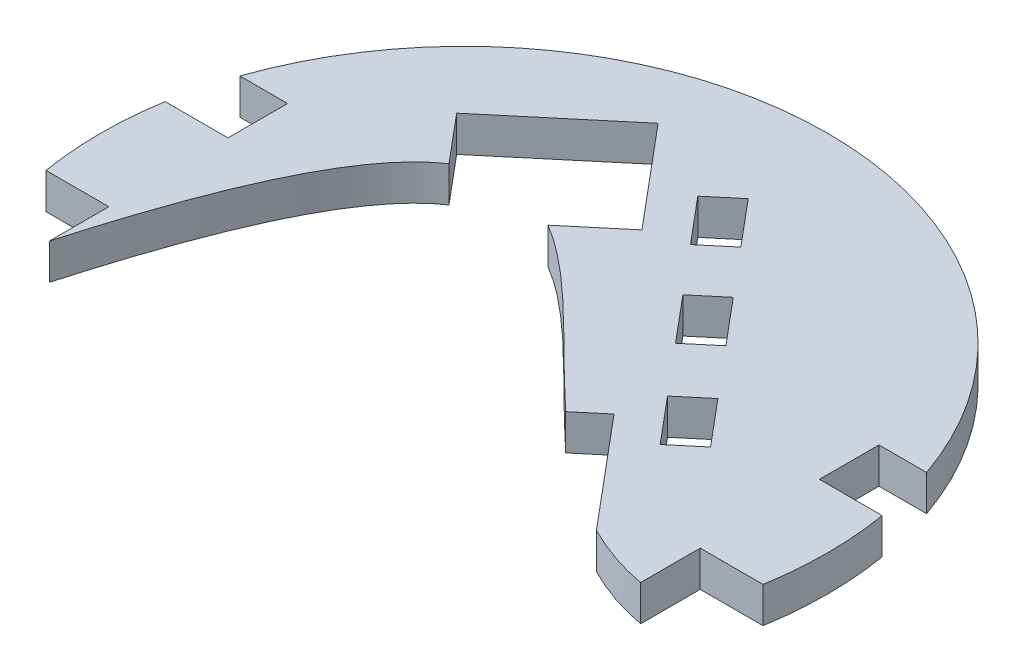
SolidWorks part; units mm, degrees
ref_plane "Alzado" through (0, 0, 0) normal (0, 0, 1) x (1, 0, 0)
ref_plane "Planta" through (0, 0, 0) normal (0, 1, 0) x (1, 0, 0)
ref_plane "Vista lateral" through (0, 0, 0) normal (1, 0, 0) x (0, 0, -1)
sketch "Croquis1" plane through (0, 0, 0) normal (0, 1, 0) x (1, 0, 0)
  circle A0 centre (0, 0) radius 30.5
extrude "Saliente-Extruir1" add sketch "Croquis1" along normal blind 3
sketch "Croquis2" plane through (0, 3, 0) normal (0, 1, 0) x (1, 0, 0)
  circle A0 centre (0, 0) radius 2
extrude "Cortar-Extruir1" cut sketch "Croquis2" against normal blind 4
sketch "Croquis5" plane through (0, 3, 0) normal (0, 1, 0) x (1, 0, 0)
  line L0 (0, 0) -> (0, 10)
  line L1 (28.8141, -5) -> (30.0874, -5)
  line L2 (28.8141, 5) -> (30.0874, 5)
  line L3 (-24.8141, 10) -> (-28.8141, 10)
  line L4 (24.8141, -5) -> (24.8141, -10)
  line L5 (-24.8141, -10) -> (-28.8141, -10)
  line L6 (24.8141, -5) -> (28.8141, -5)
  line L7 (24.8141, 5) -> (24.8141, 10)
  line L8 (-24.8141, 5) -> (-28.8141, 5)
  line L9 (-24.8141, 5) -> (-24.8141, 10)
  line L10 (-24.8141, -5) -> (-28.8141, -5)
  line L11 (-24.8141, -5) -> (-24.8141, -10)
  line L12 (24.8141, 5) -> (28.8141, 5)
  line L13 (24.8141, -10) -> (28.8141, -10)
  line L14 (24.8141, 10) -> (28.8141, 10)
  line L15 (-28.8141, 5) -> (-30.0874, 5)
  line L16 (-28.8141, -5) -> (-30.0874, -5)
  circle A1 centre (0, 0) radius 30.5 construction
  arc A2 (-28.8141, 10) -> (-30.0874, 5) centre (0, 0) ccw
  arc A3 (28.8141, 10) -> (28.8141, -10) centre (0, 0) cw
  arc A4 (-30.0874, -5) -> (-28.8141, -10) centre (0, 0) ccw
  arc A5 (30.0874, -5) -> (28.8141, -10) centre (0, 0) cw
  arc A6 (28.8141, 10) -> (30.0874, 5) centre (0, 0) cw
  circle M2 centre (0, 0) radius 30.5
extrude "Cortar-Extruir3" cut sketch "Croquis5" against normal blind 4 contours L11 L10 L8 L9 L3 L5 M2 | L15 L8 L9 L3 M2 | L14 L7 L12 L2 M2 | L4 L13 L1 L6 M2 region at (27.1844, 3, 7.3876) region at (27.1844, 3, -7.3876) region at (-27.1844, 3, 7.3876) region at (-27.1844, 3, -7.3876)
sketch "Croquis7" plane through (0, 3, 0) normal (0, 1, 0) x (1, 0, 0)
  line L0 (-8.1011, 29.1011) -> (9.5756, 8.0348)
  line L1 (-1.4002, 16.4481) -> (-0.7574, 15.682)
  line L2 (-8.1011, 29.1011) -> (-27.2522, 13.0314)
  line L3 (27.2522, -13.0314) -> (8.1011, -29.1011)
  line L4 (8.1011, -29.1011) -> (-27.2522, 13.0314)
  line L5 (1.4284, 22.4114) -> (-0.8697, 20.4831)
  line L6 (1.4284, 22.4114) -> (4.6423, 18.5812)
  line L7 (4.6423, 18.5812) -> (2.3442, 16.6528)
  line L8 (2.3442, 16.6528) -> (-0.8697, 20.4831)
  line L9 (-24.8141, -10) -> (-28.8141, -10)
  line L10 (24.8141, -10) -> (28.8141, -10)
  line L11 (9.5756, 8.0348) -> (18.4139, -2.4983)
  line L12 (18.4139, -2.4983) -> (27.2522, -13.0314)
  line L13 (11.4555, 1.1272) -> (19.169, -8.0653)
  line L14 (19.169, -8.0653) -> (9.9765, -15.7788)
  line L15 (9.9765, -15.7788) -> (2.263, -6.5863)
  line L16 (11.4555, 1.1272) -> (2.263, -6.5863)
  line L17 (-1.4002, 16.4481) -> (-7.8281, 24.1085)
  line L18 (-1.4002, 16.4481) -> (-10.5927, 8.7346)
  line L19 (-10.5927, 8.7346) -> (-17.0206, 16.3951)
  line L20 (-7.8281, 24.1085) -> (-17.0206, 16.3951)
  line L21 (16.2929, 4.6967) -> (14.6859, 6.6118)
  line L22 (16.2929, 4.6967) -> (17.8998, 2.7815)
  line L23 (14.6859, 6.6118) -> (12.3878, 4.6834)
  line L24 (17.8998, 2.7815) -> (15.6017, 0.8532)
  line L25 (15.6017, 0.8532) -> (12.3878, 4.6834)
  line L26 (-0.7574, 15.682) -> (-5.0494, 12.0807)
  arc A1 (-28.8141, -10) -> (28.8141, -10) centre (0, 0) ccw
  spline S0 degree 3 poles (24.8141, -10) (2.6081, -6.0995) (-10.3265, 41.1093) (-24.8141, -10) knots 0 0 0 0 1 1 1 1
  point P7 (-9.5756, -8.0348)
  circle M9 centre (0, 0) radius 2
  line M23 (-24.8141, -10) -> (-28.8141, -10)
  arc M24 (-28.8141, -10) -> (28.8141, -10) centre (0, 0) ccw
  line M25 (28.8141, -10) -> (24.8141, -10)
extrude "Cortar-Extruir5" cut sketch "Croquis7" against normal blind 4 contours L7 L6 L5 L0 | S0 L14 L15 L16 L18 L19 L4 L3 M9 | S0 L3 L4 M25 M23 M24 | L14 S0 L16 L15 | S0 L13 L16 | S0 L18 L17 L20 L19 | L18 S0 L19 | L24 L22 L21 L23 L11 | S0 L26 L1 L18 region at (1.8863, 3, -19.5321) region at (1.5021, 3, 7.2422) region at (-9.1912, 3, 17.0445) region at (-10.0367, 3, -11.723) region at (-9.0448, 3, -17.3632) region at (15.1438, 3, -3.7325) region at (-3.3028, 3, -14.2064) region at (13.4648, 3, 2.9154) region at (10.2518, 3, 8.0706)
sketch "Croquis9" plane through (0, 3, 0) normal (0, 1, 0) x (1, 0, 0)
  line L0 (-8.3073, 29.3469) -> (22.8679, -7.8063)
  line L2 (7.9714, 14.6138) -> (11.1854, 10.7835)
  line L3 (-8.3073, 29.3469) -> (-21.7131, 18.0981)
  line L4 (-21.7131, 18.0981) -> (9.4621, -19.0551)
  line L5 (9.4621, -19.0551) -> (22.8679, -7.8063)
  line L6 (11.1854, 10.7835) -> (8.8872, 8.8552)
  line L7 (7.9714, 14.6138) -> (5.6733, 12.6854)
  arc A1 (28.8141, 10) -> (-28.8141, 10) centre (0, 0) ccw construction
extrude "Cortar-Extruir6" cut sketch "Croquis9" against normal blind 10 contours L2 L7 L0 L6 region at (8.4293, 3, -11.7345)
